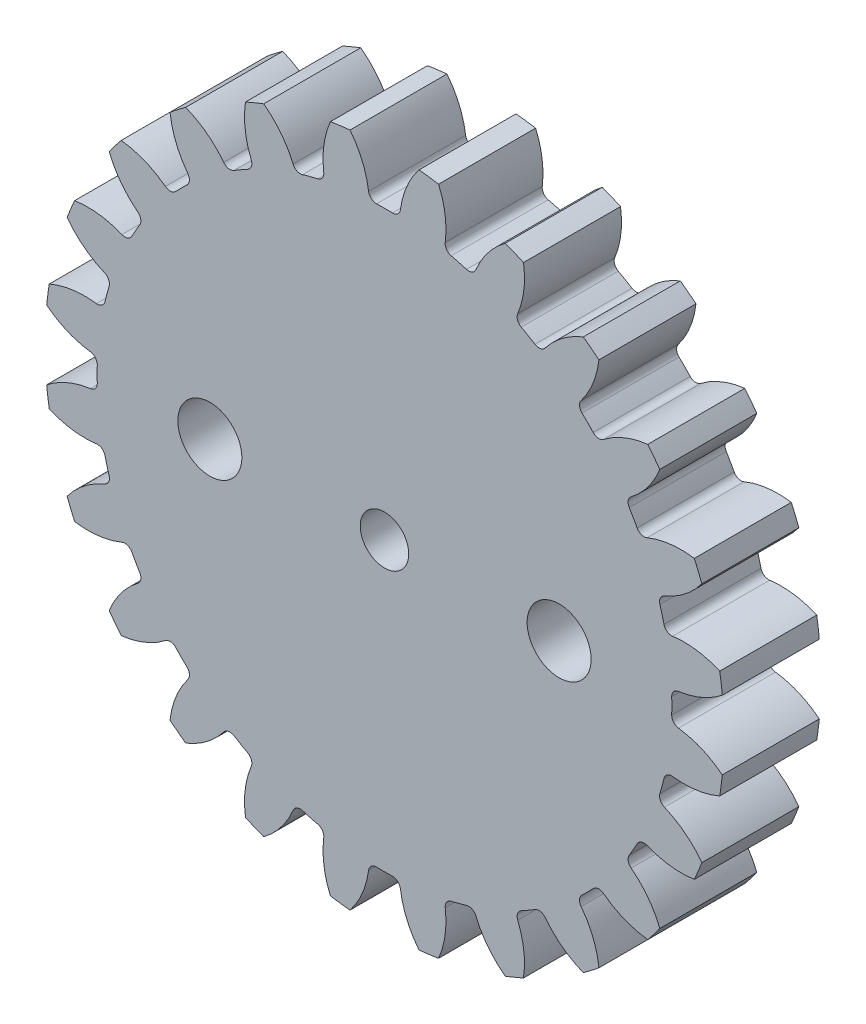
SolidWorks part; units mm, degrees
ref_plane "Front" through (0, 0, 0) normal (0, 0, 1) x (1, 0, 0)
ref_plane "Top" through (0, 0, 0) normal (0, 1, 0) x (1, 0, 0)
ref_plane "Right" through (0, 0, 0) normal (1, 0, 0) x (0, 0, -1)
sketch "Sketch1" plane through (0, 0, 0) normal (0, 0, 1) x (1, 0, 0)
  circle A0 centre (0, 0) radius 14.8077
  circle A1 centre (0, 0) radius 17.5
  circle A2 centre (0, 0) radius 16.1538
  dimension "D1" = 35
  dimension "D2" = 29.6154
  dimension "D3" = 32.3077
extrude "Boss-Extrude1" add sketch "Sketch1" along normal mid plane 5 contours A1
sketch "Sketch3" plane through (0, 0, 0) normal (0, 0, 1) x (1, 0, 0)
  line L0 (0, 0) -> (0, 17.5) construction
  line L1 (0, 0) -> (-0.785, 14.7869) construction
  line L2 (-1.0565, 16.1193) -> (1.0565, 16.1193) construction
  line L3 (-1.5345, 17.4326) -> (0, 13.2165) construction
  line L4 (0, 0) -> (2.2842, 17.3503) construction
  line L5 (1.0565, 16.1193) -> (3.1515, 15.8435) construction
  arc A0 (-0.785, 14.7869) -> (0.785, 14.7869) centre (0, 0) cw
  arc A4 (1.7783, 17.4094) -> (-1.7783, 17.4094) centre (0, 0) ccw
  circle A5 centre (0, 0) radius 17.5 construction
  arc A7 (-1.7783, 17.4094) -> (-0.785, 14.7869) centre (-5.3887, 14.5425) cw
  arc A10 (1.7783, 17.4094) -> (0.785, 14.7869) centre (5.3887, 14.5425) ccw
  circle A11 centre (0, 0) radius 14.8077 construction
  circle A12 centre (0, 0) radius 16.1538 construction
  dimension "D1" = 20
  dimension "D2" = 7.5
extrude "Cut-Extrude1" cut sketch "Sketch3" against normal through all both and the other way through all
fillet "Fillet2" radius 0.4038 2 edges at (0.785, 14.7869, 0) (-0.785, 14.7869, 0)
pattern_circular "CirPattern1" count 24 over 360 about axis through (0, 0, 2.5) along (0, 0, -1) of "Cut-Extrude1", "Fillet2"
sketch "Sketch4" plane through (0, 0, 0) normal (0, 0, 1) x (1, 0, 0)
  circle A0 centre (0, 0) radius 1.25
  dimension "D1" = 2.5
extrude "Through_Center_Hole" cut sketch "Sketch4" against normal through all both and the other way through all
sketch "Sketch5" plane through (0, 0, 0) normal (0, 0, 1) x (1, 0, 0)
  line L0 (-9, 0) -> (9, 0) construction
  circle A0 centre (9, 0) radius 1.65
  circle A1 centre (-9, 0) radius 1.65
  dimension "D2" = 3.3
  dimension "D1" = 18
extrude "To_Knuckle_Mount" cut sketch "Sketch5" against normal through all both and the other way through all
equation "\"od\"= 35'outside diameter"
equation "\"n\"= 24'number of teeth"
equation "\"m\"= \"od\" / ( \"n\" + 2 )'module"
equation "\"p\"= \"m\" * pi'pitch"
equation "\"d\"= \"m\" * \"n\"'primitive diameter"
equation "\"da\"= \"d\" + 2 * \"m\"'head diamater"
equation "\"df\"= \"d\" - 2 * \"m\"'foot diameter"
equation "\"D1@Sketch1\"=\"od\""
equation "\"D2@Sketch1\"=\"df\""
equation "\"D3@Sketch1\"=\"d\""
equation "\"D2@Sketch3\"=180/\"n\""
equation "\"D1@Fillet2\"=.3*\"m\""
equation "\"D1@CirPattern1\"=\"n\""
